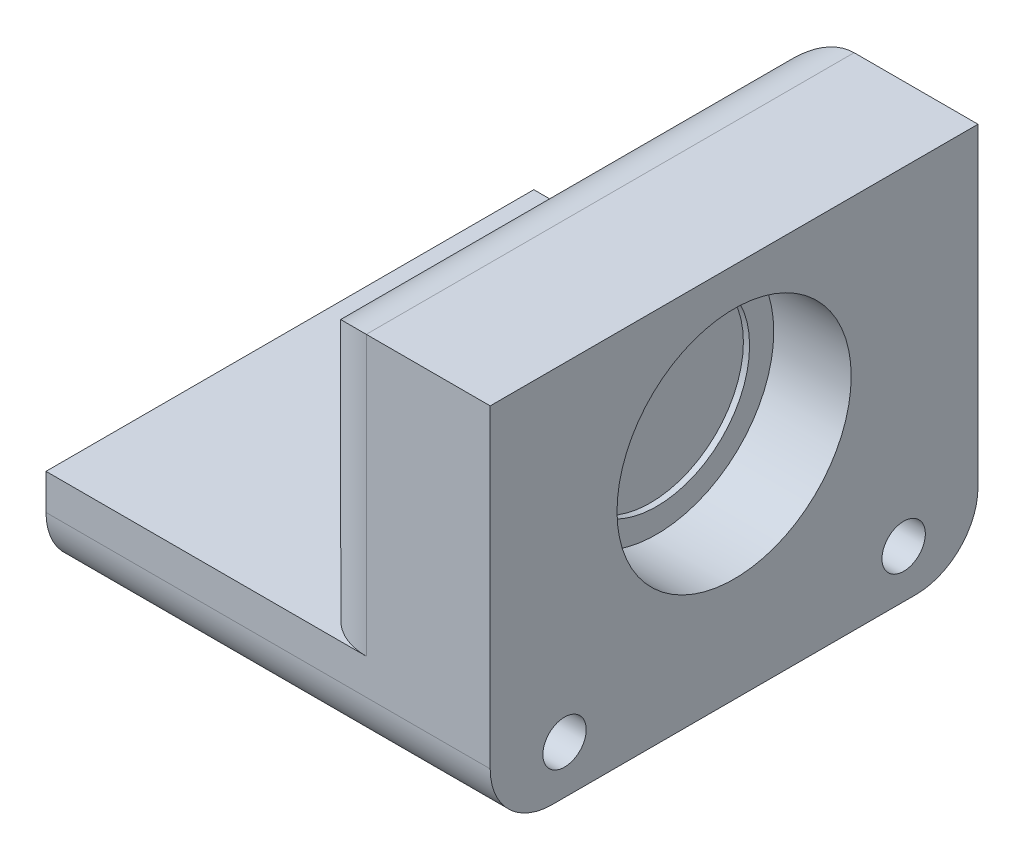
SolidWorks part; units mm, degrees
ref_plane "Front Plane" through (0, 0, 0) normal (0, 0, 1) x (1, 0, 0)
ref_plane "Top Plane" through (0, 0, 0) normal (0, 1, 0) x (1, 0, 0)
ref_plane "Right Plane" through (0, 0, 0) normal (1, 0, 0) x (0, 0, -1)
sketch "Sketch1" plane through (0, 0, 0) normal (0, 0, 1) x (1, 0, 0)
  line L0 (-71.7423, 0) -> (-71.7423, -4)
  line L1 (-71.7423, -4) -> (-53.5305, -4)
  line L2 (-53.5305, -4) -> (-53.5305, 11.43)
  line L3 (-53.5305, 11.43) -> (-61.1505, 11.43)
  line L4 (-61.1505, 11.43) -> (-61.1505, 0)
  line L5 (-61.1505, 0) -> (-71.7423, 0)
  dimension "D1" = 4
  dimension "D2" = 18.2118
  dimension "D3" = 15.43
  dimension "D4" = 10.5918
extrude "Boss-Extrude1" add sketch "Sketch1" against normal blind 20
sketch "Sketch2" plane through (-71.7423, 0, 0) normal (-1, 0, 0) x (0, 0, 1)
  line L0 (-10, 0) -> (-10, -4) construction
  line L1 (-20, 0) -> (0, 0) construction
  line L2 (-20, -4) -> (0, -4) construction
  line L3 (-20, -2) -> (0, -2) construction
  line L4 (-20, 0) -> (-20, -4) construction
  line L5 (0, 0) -> (0, -4) construction
  circle A0 centre (-12.286, -2) radius 1.27
  circle A1 centre (-7.714, -2) radius 1.27
  dimension "D1" = 2.54
  dimension "D2" = 2.286
extrude "Cut-Extrude1" cut sketch "Sketch2" against normal blind 4
sketch "Sketch3" plane through (-61.1505, 0, 0) normal (-1, 0, 0) x (0, 0, 1)
  line L0 (-10, 11.43) -> (-10, 0) construction
  line L1 (-20, 11.43) -> (0, 11.43) construction
  line L2 (-20, 0) -> (0, 0) construction
  circle A0 centre (-10, 5.08) radius 4.8006
  dimension "D1" = 5.08
extrude "Cut-Extrude2" cut sketch "Sketch3" against normal blind 3.175 contours A0
sketch "Sketch4" plane through (-57.9755, 0, 0) normal (-1, 0, 0) x (0, 0, 1)
  circle A0 centre (-10, 5.08) radius 3.81
extrude "Cut-Extrude3" cut sketch "Sketch4" against normal blind 0.254
sketch "Sketch5" plane through (-53.5305, 0, 0) normal (1, 0, 0) x (0, 0, -1)
  line L0 (0, 0) -> (20, 0) construction
  line L1 (10, 11.43) -> (10, 0) construction
  line L2 (20, 11.43) -> (0, 11.43) construction
  circle A0 centre (10, 5.08) radius 4.8006
  dimension "D2" = 9.6012
  dimension "D1" = 5.08
extrude "Cut-Extrude4" cut sketch "Sketch5" against normal blind 3.175
sketch "Sketch6" plane through (-56.7055, 0, 0) normal (1, 0, 0) x (0, 0, -1)
  circle A0 centre (10, 5.08) radius 3.81
extrude "Cut-Extrude5" cut sketch "Sketch6" against normal blind 0.254
sketch "Sketch7" plane through (-67.7423, 0, 0) normal (-1, 0, 0) x (0, 0, 1)
  line L0 (-20, 0) -> (0, 0) construction
  line L1 (-20, 0) -> (-20, -4) construction
  line L2 (-10, 0) -> (-10, -4) construction
  line L3 (-20, -4) -> (0, -4) construction
  point P0 (-16.952, -2.032)
  point P9 (-3.048, -2.032)
  dimension "D1" = 2.032
  dimension "D2" = 3.048
hole_wizard "CBORE for #0 Socket Head Cap Screw1" positions "Sketch9" profile "Sketch8" counterbore size "#0" standard "ANSI Inch" end condition through all
sketch "Sketch9" plane through (-71.7423, 0, 0) normal (-1, 0, 0) x (0, 0, 1)
  point P0 (-16.952, -2.032)
  point P3 (-3.048, -2.032)
sketch "Sketch8" plane through (-71.7423, -2.032, -16.952) normal (0, 1, 0) x (0, 0, 1)
  line L0 (0, 0) -> (0, 18.2118)
  line L1 (0, 18.2118) -> (0.889, 18.2118)
  line L3 (0.889, 18.2118) -> (0.889, 14.732)
  line L4 (0.889, 14.732) -> (1.5875, 14.732)
  line L5 (1.5875, 14.732) -> (1.5875, 0)
  line L7 (1.5875, 0) -> (0, 0)
  line L11 (0, -6.35) -> (0, 107.95) construction
  dimension "Thru Hole Dia." = 1.778
  dimension "Thru Hole Depth" = 18.2118
  dimension "C'Bore Dia." = 3.175
  dimension "C'Bore Depth" = 14.732
fillet "Fillet1" radius 2.54 5 edges at (-61.1505, 5.715, -20) (-61.1505, 11.43, -10) (-61.1505, 5.715, 0) (-62.6364, -4, 0) (-62.6364, -4, -20)
